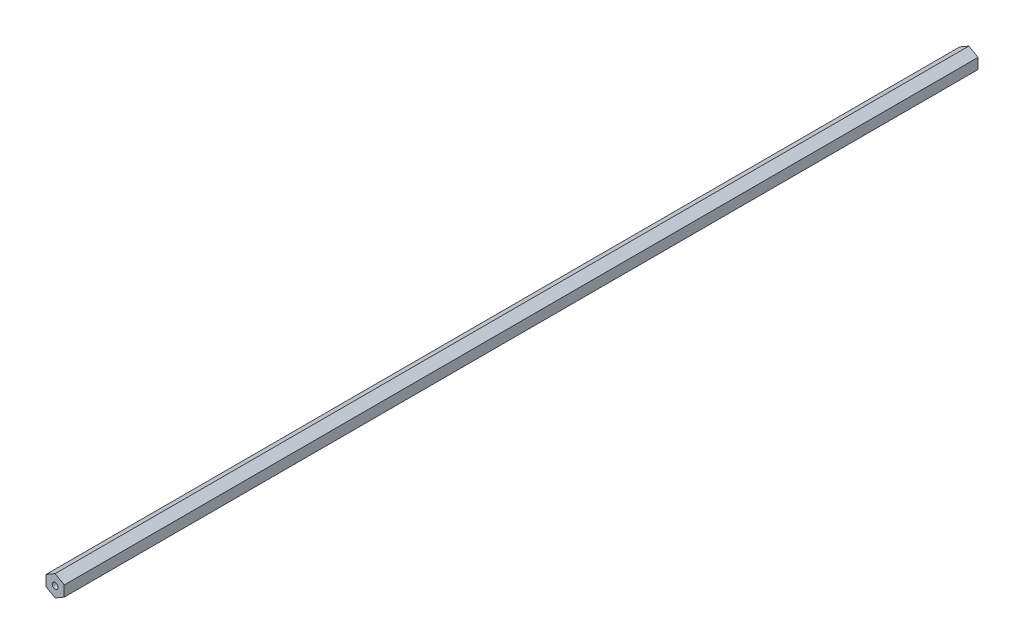
SolidWorks part; units mm, degrees
ref_plane "Front Plane" through (0, 0, 0) normal (0, 0, 1) x (1, 0, 0)
ref_plane "Top Plane" through (0, 0, 0) normal (0, 1, 0) x (1, 0, 0)
ref_plane "Right Plane" through (0, 0, 0) normal (1, 0, 0) x (0, 0, -1)
sketch "Sketch1" plane through (0, 0, 0) normal (0, 0, 1) x (1, 0, 0)
  line L1 (6.35, -3.6662) -> (6.35, 3.6662)
  line L2 (6.35, 3.6662) -> (0, 7.3323)
  line L3 (0, 7.3323) -> (-6.35, 3.6662)
  line L4 (-6.35, 3.6662) -> (-6.35, -3.6662)
  line L5 (-6.35, -3.6662) -> (0, -7.3323)
  line L6 (0, -7.3323) -> (6.35, -3.6662)
  circle A0 centre (0, 0) radius 6.35 construction
  dimension "D1" = 12.7
extrude "Boss-Extrude1" add sketch "Sketch1" along normal mid plane 636.0846
sketch "Sketch2" plane through (0, 0, 318.0423) normal (0, 0, 1) x (1, 0, 0)
  circle A0 centre (0, 0) radius 2.4892
  dimension "D1" = 4.9784
hole_wizard "#10-32 Tapped Hole1" positions "3DSketch1" profile "Sketch3" tap size "#10-32" standard "ANSI Inch"
sketch3d "3DSketch1"
  line L1 (-6.35, 3.6662, -318.0423) -> (-6.35, -3.6662, -318.0423) construction
  point P0 (0, 0, 318.0423)
  point P3 (0, 0, -318.0423)
  point P13 (-6.35, 0, -318.0423)
sketch "Sketch3" plane through (0, 0, 318.0423) normal (1, 0, 0) x (0, -1, 0)
  line L0 (0, 0) -> (0, 17.5608)
  line L1 (0, 17.5608) -> (2.0193, 16.3474)
  line L2 (2.0193, 16.3474) -> (2.0193, 0)
  line L5 (2.0193, 0) -> (0, 0)
  line L10 (0, 17.5608) -> (-2.0193, 16.3474) construction
  line L11 (0, -6.35) -> (0, 107.95) construction
  dimension "Tap Drill Dia." = 4.0386
  dimension "Tap Drill Depth" = 16.3474
  dimension "Drill Angle" = 118
cosmetic thread "Hole Thread1" parameters "D1"=13.97, "D2"=4.826
cosmetic thread "Hole Thread2" parameters "D1"=13.97, "D2"=4.826
